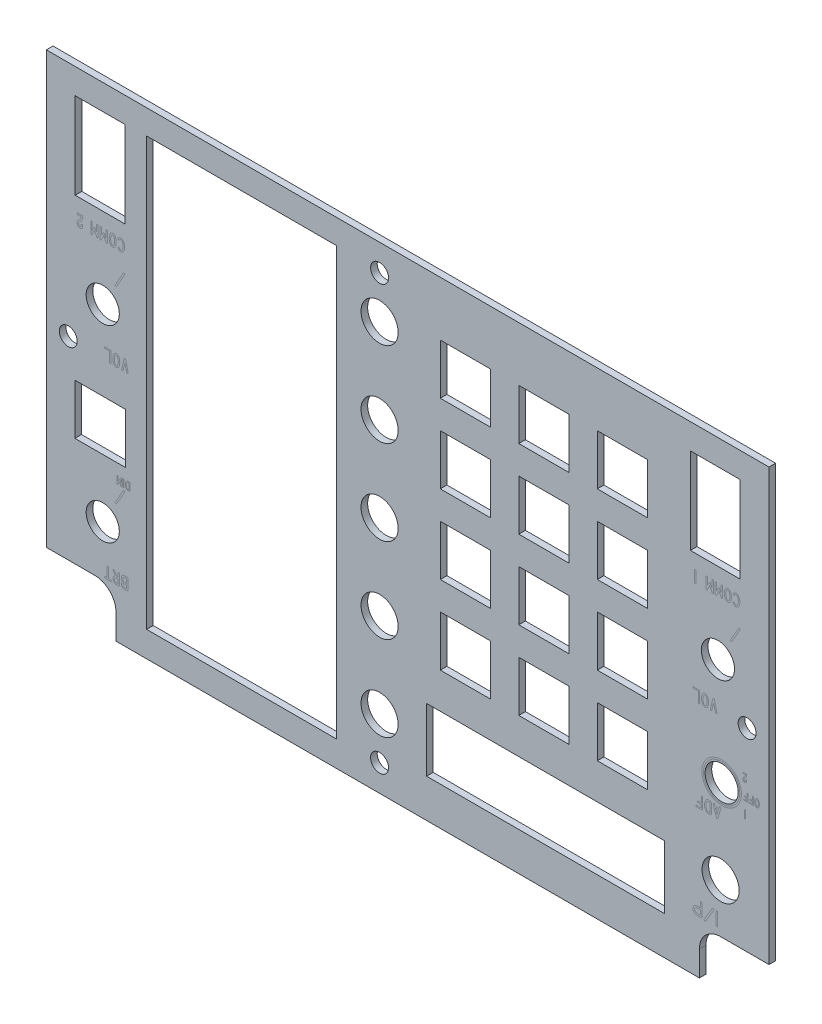
SolidWorks part; units mm, degrees
material "ABS PC"
ref_plane "Front Plane" through (0, 0, 0) normal (0, 0, 1) x (1, 0, 0)
ref_plane "Top Plane" through (0, 0, 0) normal (0, 1, 0) x (1, 0, 0)
ref_plane "Right Plane" through (0, 0, 0) normal (1, 0, 0) x (0, 0, -1)
sketch "Sketch1" plane through (0, 0, 0) normal (0, 0, 1) x (1, 0, 0)
  line L8 (74.93, -171.1167) -> (86.5187, -171.1167)
  line L9 (86.5187, -171.1167) -> (86.5187, -67.9292)
  line L10 (86.5187, -67.9292) -> (-86.5187, -67.9292)
  line L11 (-86.5187, -67.9292) -> (-86.5187, -171.1167)
  line L12 (-86.5187, -171.1167) -> (-74.93, -171.1167)
  line L13 (-69.85, -176.1967) -> (-69.85, -182.2292)
  line L14 (-69.85, -182.2292) -> (69.85, -182.2292)
  line L15 (69.85, -182.2292) -> (69.85, -176.1967)
  line L16 (74.93, -171.1167) -> (86.5187, -171.1167)
  line L17 (86.5187, -171.1167) -> (86.5187, -67.9292)
  line L18 (86.5187, -67.9292) -> (-86.5187, -67.9292)
  line L19 (-86.5187, -67.9292) -> (-86.5187, -171.1167)
  line L20 (-86.5187, -171.1167) -> (-74.93, -171.1167)
  line L21 (-69.85, -176.1967) -> (-69.85, -182.2292)
  line L22 (-69.85, -182.2292) -> (69.85, -182.2292)
  line L23 (69.85, -182.2292) -> (69.85, -176.1967)
  arc A2 (-69.85, -176.1967) -> (-74.93, -171.1167) centre (-74.93, -176.1967) ccw
  arc A3 (74.93, -171.1167) -> (69.85, -176.1967) centre (74.93, -176.1967) ccw
  arc A4 (-69.85, -176.1967) -> (-74.93, -171.1167) centre (-74.93, -176.1967) ccw
  arc A5 (74.93, -171.1167) -> (69.85, -176.1967) centre (74.93, -176.1967) ccw
  dimension "D1" = 0
extrude "Boss-Extrude1" add sketch "Sketch1" against normal blind 1.5875
sketch "Sketch3" plane through (0, 0, 0) normal (0, 0, 1) x (1, 0, 0)
  line L0 (-67.6275, -133.0167) -> (-79.6925, -133.0167) construction
  line L1 (-79.6925, -133.0167) -> (-79.6925, -145.0817) construction
  line L2 (-79.6925, -145.0817) -> (-67.6275, -145.0817) construction
  line L3 (-67.6275, -145.0817) -> (-67.6275, -133.0167) construction
  line L4 (19.8755, -149.3997) -> (19.8755, -137.3347) construction
  line L5 (19.8755, -137.3347) -> (7.8105, -137.3347) construction
  line L6 (7.8105, -137.3347) -> (7.8105, -149.3997) construction
  line L7 (7.8105, -149.3997) -> (19.8755, -149.3997) construction
  line L8 (38.6715, -149.3997) -> (38.6715, -137.3347) construction
  line L9 (38.6715, -137.3347) -> (26.6065, -137.3347) construction
  line L10 (26.6065, -137.3347) -> (26.6065, -149.3997) construction
  line L11 (26.6065, -149.3997) -> (38.6715, -149.3997) construction
  line L12 (45.4025, -149.3997) -> (57.4675, -149.3997) construction
  line L13 (57.4675, -149.3997) -> (57.4675, -137.3347) construction
  line L14 (57.4675, -137.3347) -> (45.4025, -137.3347) construction
  line L15 (45.4025, -137.3347) -> (45.4025, -149.3997) construction
  line L16 (57.4675, -130.6037) -> (57.4675, -118.5387) construction
  line L17 (57.4675, -118.5387) -> (45.4025, -118.5387) construction
  line L18 (45.4025, -118.5387) -> (45.4025, -130.6037) construction
  line L19 (45.4025, -130.6037) -> (57.4675, -130.6037) construction
  line L20 (38.6715, -130.6037) -> (38.6715, -118.5387) construction
  line L21 (38.6715, -118.5387) -> (26.6065, -118.5387) construction
  line L22 (26.6065, -118.5387) -> (26.6065, -130.6037) construction
  line L23 (26.6065, -130.6037) -> (38.6715, -130.6037) construction
  line L24 (19.8755, -130.6037) -> (19.8755, -118.5387) construction
  line L25 (19.8755, -118.5387) -> (7.8105, -118.5387) construction
  line L26 (7.8105, -118.5387) -> (7.8105, -130.6037) construction
  line L27 (7.8105, -130.6037) -> (19.8755, -130.6037) construction
  line L28 (19.8755, -111.8077) -> (19.8755, -99.7427) construction
  line L29 (19.8755, -99.7427) -> (7.8105, -99.7427) construction
  line L30 (7.8105, -99.7427) -> (7.8105, -111.8077) construction
  line L31 (7.8105, -111.8077) -> (19.8755, -111.8077) construction
  line L32 (19.8755, -93.0117) -> (19.8755, -80.9467) construction
  line L33 (19.8755, -80.9467) -> (7.8105, -80.9467) construction
  line L34 (7.8105, -80.9467) -> (7.8105, -93.0117) construction
  line L35 (7.8105, -93.0117) -> (19.8755, -93.0117) construction
  line L36 (38.6715, -93.0117) -> (38.6715, -80.9467) construction
  line L37 (38.6715, -80.9467) -> (26.6065, -80.9467) construction
  line L38 (26.6065, -80.9467) -> (26.6065, -93.0117) construction
  line L39 (26.6065, -93.0117) -> (38.6715, -93.0117) construction
  line L40 (38.6715, -111.8077) -> (38.6715, -99.7427) construction
  line L41 (38.6715, -99.7427) -> (26.6065, -99.7427) construction
  line L42 (26.6065, -99.7427) -> (26.6065, -111.8077) construction
  line L43 (26.6065, -111.8077) -> (38.6715, -111.8077) construction
  line L44 (57.4675, -111.8077) -> (57.4675, -99.7427) construction
  line L45 (57.4675, -99.7427) -> (45.4025, -99.7427) construction
  line L46 (45.4025, -99.7427) -> (45.4025, -111.8077) construction
  line L47 (45.4025, -111.8077) -> (57.4675, -111.8077) construction
  line L48 (57.4675, -93.0117) -> (57.4675, -80.9467) construction
  line L49 (57.4675, -80.9467) -> (45.4025, -80.9467) construction
  line L50 (45.4025, -80.9467) -> (45.4025, -93.0117) construction
  line L51 (45.4025, -93.0117) -> (57.4675, -93.0117) construction
  line L52 (-67.6275, -133.0167) -> (-79.6925, -133.0167)
  line L53 (-79.6925, -133.0167) -> (-79.6925, -145.0817)
  line L54 (-79.6925, -145.0817) -> (-67.6275, -145.0817)
  line L55 (-67.6275, -145.0817) -> (-67.6275, -133.0167)
  line L56 (19.8755, -149.3997) -> (19.8755, -137.3347)
  line L57 (19.8755, -137.3347) -> (7.8105, -137.3347)
  line L58 (7.8105, -137.3347) -> (7.8105, -149.3997)
  line L59 (7.8105, -149.3997) -> (19.8755, -149.3997)
  line L60 (38.6715, -149.3997) -> (38.6715, -137.3347)
  line L61 (38.6715, -137.3347) -> (26.6065, -137.3347)
  line L62 (26.6065, -137.3347) -> (26.6065, -149.3997)
  line L63 (26.6065, -149.3997) -> (38.6715, -149.3997)
  line L64 (45.4025, -149.3997) -> (57.4675, -149.3997)
  line L65 (57.4675, -149.3997) -> (57.4675, -137.3347)
  line L66 (57.4675, -137.3347) -> (45.4025, -137.3347)
  line L67 (45.4025, -137.3347) -> (45.4025, -149.3997)
  line L68 (57.4675, -130.6037) -> (57.4675, -118.5387)
  line L69 (57.4675, -118.5387) -> (45.4025, -118.5387)
  line L70 (45.4025, -118.5387) -> (45.4025, -130.6037)
  line L71 (45.4025, -130.6037) -> (57.4675, -130.6037)
  line L72 (38.6715, -130.6037) -> (38.6715, -118.5387)
  line L73 (38.6715, -118.5387) -> (26.6065, -118.5387)
  line L74 (26.6065, -118.5387) -> (26.6065, -130.6037)
  line L75 (26.6065, -130.6037) -> (38.6715, -130.6037)
  line L76 (19.8755, -130.6037) -> (19.8755, -118.5387)
  line L77 (19.8755, -118.5387) -> (7.8105, -118.5387)
  line L78 (7.8105, -118.5387) -> (7.8105, -130.6037)
  line L79 (7.8105, -130.6037) -> (19.8755, -130.6037)
  line L80 (19.8755, -111.8077) -> (19.8755, -99.7427)
  line L81 (19.8755, -99.7427) -> (7.8105, -99.7427)
  line L82 (7.8105, -99.7427) -> (7.8105, -111.8077)
  line L83 (7.8105, -111.8077) -> (19.8755, -111.8077)
  line L84 (19.8755, -93.0117) -> (19.8755, -80.9467)
  line L85 (19.8755, -80.9467) -> (7.8105, -80.9467)
  line L86 (7.8105, -80.9467) -> (7.8105, -93.0117)
  line L87 (7.8105, -93.0117) -> (19.8755, -93.0117)
  line L88 (38.6715, -93.0117) -> (38.6715, -80.9467)
  line L89 (38.6715, -80.9467) -> (26.6065, -80.9467)
  line L90 (26.6065, -80.9467) -> (26.6065, -93.0117)
  line L91 (26.6065, -93.0117) -> (38.6715, -93.0117)
  line L92 (38.6715, -111.8077) -> (38.6715, -99.7427)
  line L93 (38.6715, -99.7427) -> (26.6065, -99.7427)
  line L94 (26.6065, -99.7427) -> (26.6065, -111.8077)
  line L95 (26.6065, -111.8077) -> (38.6715, -111.8077)
  line L96 (57.4675, -111.8077) -> (57.4675, -99.7427)
  line L97 (57.4675, -99.7427) -> (45.4025, -99.7427)
  line L98 (45.4025, -99.7427) -> (45.4025, -111.8077)
  line L99 (45.4025, -111.8077) -> (57.4675, -111.8077)
  line L100 (57.4675, -93.0117) -> (57.4675, -80.9467)
  line L101 (57.4675, -80.9467) -> (45.4025, -80.9467)
  line L102 (45.4025, -80.9467) -> (45.4025, -93.0117)
  line L103 (45.4025, -93.0117) -> (57.4675, -93.0117)
  circle A0 centre (74.93, -159.3692) radius 4.445 construction
  circle A1 centre (-6.731, -165.7192) radius 4.445 construction
  circle A2 centre (-6.731, -145.3992) radius 4.445 construction
  circle A3 centre (-6.731, -125.0792) radius 4.445 construction
  circle A4 centre (-6.731, -104.7592) radius 4.445 construction
  circle A5 centre (-6.731, -84.4392) radius 4.445 construction
  circle A6 centre (74.93, -159.3692) radius 4.445
  circle A7 centre (-6.731, -165.7192) radius 4.445
  circle A8 centre (-6.731, -145.3992) radius 4.445
  circle A9 centre (-6.731, -125.0792) radius 4.445
  circle A10 centre (-6.731, -104.7592) radius 4.445
  circle A11 centre (-6.731, -84.4392) radius 4.445
extrude "Cut-Extrude1" cut sketch "Sketch3" against normal through all
sketch "Sketch4" plane through (0, 0, 0) normal (0, 0, 1) x (1, 0, 0)
  circle A0 centre (-73.025, -113.9667) radius 3.9688
  circle A1 centre (-73.025, -159.0517) radius 3.9688
  circle A2 centre (74.295, -113.9667) radius 3.9688
  circle A3 centre (75.184, -139.0492) radius 3.9687
  dimension "D1" = 7.9375
extrude "Cut-Extrude2" cut sketch "Sketch4" against normal through all
sketch "Sketch5" plane through (0, 0, 0) normal (0, 0, 1) x (1, 0, 0)
  line L0 (-79.63, -73.9922) -> (-79.63, -94.6322)
  line L1 (-79.63, -94.6322) -> (-67.69, -94.6322)
  line L2 (-67.69, -94.6322) -> (-67.69, -73.9922)
  line L3 (-67.69, -73.9922) -> (-79.63, -73.9922)
  line L4 (-78.36, -75.2622) -> (-78.36, -93.3622)
  line L5 (-78.36, -93.3622) -> (-68.96, -93.3622)
  line L6 (-68.96, -93.3622) -> (-68.96, -75.2622)
  line L7 (-68.96, -75.2622) -> (-78.36, -75.2622)
  line L8 (-78.36, -75.2622) -> (-78.36, -93.3622) construction
  line L9 (-78.36, -93.3622) -> (-68.96, -93.3622) construction
  line L10 (-68.96, -93.3622) -> (-68.96, -75.2622) construction
  line L11 (-68.96, -75.2622) -> (-78.36, -75.2622) construction
  line L12 (68.96, -75.2622) -> (68.96, -93.3622)
  line L13 (68.96, -93.3622) -> (78.36, -93.3622)
  line L14 (78.36, -93.3622) -> (78.36, -75.2622)
  line L15 (78.36, -75.2622) -> (68.96, -75.2622)
  line L16 (68.96, -75.2622) -> (68.96, -93.3622) construction
  line L17 (68.96, -93.3622) -> (78.36, -93.3622) construction
  line L18 (78.36, -93.3622) -> (78.36, -75.2622) construction
  line L19 (78.36, -75.2622) -> (68.96, -75.2622) construction
  line L20 (67.69, -73.9922) -> (67.69, -94.6322)
  line L21 (67.69, -94.6322) -> (79.63, -94.6322)
  line L22 (79.63, -94.6322) -> (79.63, -73.9922)
  line L23 (79.63, -73.9922) -> (67.69, -73.9922)
  line L24 (-61.06, -75.0622) -> (-51.66, -75.0622) construction
  line L25 (-62.53, -73.7922) -> (-17.068, -73.7922)
  line L26 (-62.53, -73.7922) -> (-62.53, -176.1122)
  line L27 (-62.53, -176.1122) -> (-17.068, -176.1122)
  line L28 (-17.068, -73.7922) -> (-17.068, -176.1122)
  line L29 (-62.53, -73.7922) -> (-17.068, -176.1122) construction
  line L30 (-62.53, -176.1122) -> (-17.068, -73.7922) construction
  line L31 (-61.26, -93.3622) -> (-61.26, -75.2622) construction
  line L32 (-51.66, -174.8422) -> (-61.06, -174.8422) construction
  line L33 (-18.338, -167.7344) -> (-18.338, -169.4031) construction
  line L34 (61.52, -158.4422) -> (61.52, -172.5422) construction
  line L35 (5.02, -157.9422) -> (61.02, -157.9422) construction
  line L36 (61.02, -173.0422) -> (5.02, -173.0422) construction
  line L37 (4.52, -172.5422) -> (4.52, -158.4422) construction
  line L38 (61.52, -157.9422) -> (61.52, -173.0422)
  line L39 (4.52, -157.9422) -> (61.52, -157.9422)
  line L40 (61.52, -173.0422) -> (4.52, -173.0422)
  line L41 (4.52, -173.0422) -> (4.52, -157.9422)
  point P20 (-39.799, -124.9522)
  dimension "D4" = 1.27
  dimension "D5" = 1.27
  dimension "D6" = 1.27
  dimension "D7" = 1.27
  dimension "D1" = 0
  dimension "D2" = 0
  dimension "D3" = 1.27
extrude "Cut-Extrude3" cut sketch "Sketch5" against normal through all
sketch "Sketch8" plane through (0, 0, 0) normal (0, 0, 1) x (1, 0, 0)
  line L0 (74.93, -166.1955) -> (67.9869, -166.1955) construction
  line L1 (75.184, -144.236) -> (70.4533, -144.236) construction
  line L3 (79.9147, -139.0492) -> (84.3094, -139.0492) construction
  line L4 (84.3094, -139.0492) -> (84.3094, -138.1094) construction
  line L5 (84.3094, -138.1094) -> (79.9147, -138.1094) construction
  line L6 (79.9147, -139.0492) -> (79.9147, -143.78) construction
  line L7 (79.9147, -139.0492) -> (79.9147, -134.3185) construction
  line L8 (79.9147, -134.3185) -> (84.3094, -134.3185) construction
  line L9 (79.9147, -143.78) -> (84.3094, -143.78) construction
  line L10 (79.9147, -141.9004) -> (84.3094, -141.9004) construction
  line L11 (66.548, -98.0282) -> (80.772, -98.0282) construction
  line L12 (66.548, -98.0282) -> (80.772, -98.0282) construction
  line L13 (74.295, -122.5456) -> (67.945, -122.5456) construction
  line L14 (74.295, -113.9667) -> (77.47, -108.4675) construction
  line L15 (77.47, -108.4675) -> (79.375, -105.1679) construction
  line L16 (77.635, -108.5627) -> (79.54, -105.2632)
  line L17 (77.305, -108.3722) -> (79.21, -105.0727)
  line L18 (-73.025, -122.5456) -> (-79.375, -122.5456) construction
  line L19 (-73.025, -122.5456) -> (-66.675, -122.5456) construction
  line L20 (-73.025, -113.9667) -> (-69.85, -108.4675) construction
  line L21 (-73.025, -167.6306) -> (-79.375, -167.6306) construction
  line L22 (-69.85, -108.4675) -> (-67.945, -105.1679) construction
  line L23 (-73.025, -159.0517) -> (-69.85, -153.5525) construction
  line L24 (-73.025, -167.6306) -> (-66.675, -167.6306) construction
  line L25 (-69.85, -153.5525) -> (-67.945, -150.2529) construction
  line L26 (-69.685, -108.5627) -> (-67.78, -105.2632)
  line L27 (-70.015, -108.3722) -> (-68.11, -105.0727)
  line L28 (-69.685, -153.6477) -> (-67.78, -150.3482)
  line L29 (-70.015, -153.4572) -> (-68.11, -150.1577)
  line L30 (0, -182.2292) -> (0, -67.9292) construction
  line L31 (-69.85, -182.2292) -> (69.85, -182.2292) construction
  line L32 (86.5187, -67.9292) -> (-86.5187, -67.9292) construction
  line L33 (-66.548, -98.0282) -> (-80.772, -98.0282) construction
  line L34 (-65.0763, -147.6617) -> (-71.1398, -147.6617) construction
  line L35 (-67.945, -150.2529) -> (-66.4489, -147.6617) construction
  circle A0 centre (74.93, -159.3692) radius 6.8263 construction
  circle A1 centre (75.184, -139.0492) radius 3.9687 construction
  circle A2 centre (75.184, -139.0492) radius 3.9687 construction
  circle A3 centre (75.184, -139.0492) radius 4.3497
  circle A4 centre (75.184, -139.0492) radius 4.7307
  circle A5 centre (74.295, -113.9667) radius 6.35 construction
  circle A6 centre (-73.025, -113.9667) radius 6.35 construction
  arc A8 (77.635, -108.5627) -> (77.305, -108.3722) centre (77.47, -108.4675) cw
  arc A9 (79.54, -105.2632) -> (79.21, -105.0727) centre (79.375, -105.1679) ccw
  circle A11 centre (-73.025, -159.0517) radius 6.35 construction
  arc A12 (-69.685, -108.5627) -> (-70.015, -108.3722) centre (-69.85, -108.4675) cw
  arc A13 (-67.78, -105.2632) -> (-68.11, -105.0727) centre (-67.945, -105.1679) ccw
  arc A14 (-69.685, -153.6477) -> (-70.015, -153.4572) centre (-69.85, -153.5525) cw
  arc A15 (-67.78, -150.3482) -> (-68.11, -150.1577) centre (-67.945, -150.2529) ccw
  text T0 "I/P" font "GordonURWMed" height in points 14
  text T1 "ADF" font "GordonURWCon" height in points 12
  text T2 "VOL"
  text T3 "OFF" font "GordonURWCon" height in points 8
  text T4 "1" font "GordonURWCon" height in points 8
  text T5 "2" font "GordonURWCon" height in points 8
  text T6 "COMM 1"
  text T7 "VOL"
  text T8 "BRT"
  text T9 "VOL"
  text T10 "COMM 2"
  text T11 "DIM" font "GordonURWCon" height in points 8
  point P19 (74.295, -120.3167)
  point P20 (67.945, -113.9667)
  point P26 (75.184, -143.78)
  point P30 (75.184, -134.3185)
  point P49 (-73.025, -120.3167)
  point P50 (-79.375, -113.9667)
  point P56 (-66.675, -113.9667)
  point P63 (-73.025, -165.4017)
  point P64 (-79.375, -159.0517)
  point P67 (-66.675, -159.0517)
  point P92 (-66.4489, -147.6617)
  dimension "D1" = 0.381
  dimension "D3" = 12.7
  dimension "D11" = 12.7
  dimension "D14" = 12.7
  dimension "D4" = 0.9398
  dimension "D5" = 8.7892
  dimension "D6" = 1.8796
  dimension "D7" = 30
  dimension "D8" = 0.1905
  dimension "D10" = 3.81
  dimension "D12" = 3.81
  dimension "D13" = 60
  dimension "D15" = 3.81
  dimension "D16" = 60
  dimension "D17" = 8.5788
  dimension "D2" = 0.381
  dimension "D9" = 0.1905
  dimension "D18" = 0.1905
  dimension "D19" = 0.1905
  dimension "D20" = 0.1905
  dimension "D21" = 0.1905
split line "Split Line1"
hole_wizard "#6 Clearance Hole2" positions "Sketch9" profile "Sketch10" hole size "#6" standard "ANSI Inch" end condition through all
sketch "Sketch9" plane through (0, 0, 0) normal (0, 0, 1) x (-1, 0, 0)
  point P0 (-81.28, 124.6982)
  point P3 (6.731, 175.8792)
  point P6 (81.28, 124.6982)
  point P9 (6.731, 74.2792)
sketch "Sketch10" plane through (81.28, -124.6982, 0) normal (1, 0, 0) x (0, -1, 0)
  line L0 (0, 0) -> (0, 1.5875)
  line L1 (0, 1.5875) -> (2.1526, 1.5875)
  line L2 (2.1526, 1.5875) -> (2.1526, 0)
  line L3 (2.1526, 0) -> (0, 0)
  line L4 (0, -6.35) -> (0, 107.95) construction
  dimension "Thru Hole Dia." = 4.3053
  dimension "Thru Hole Depth" = 1.5875
